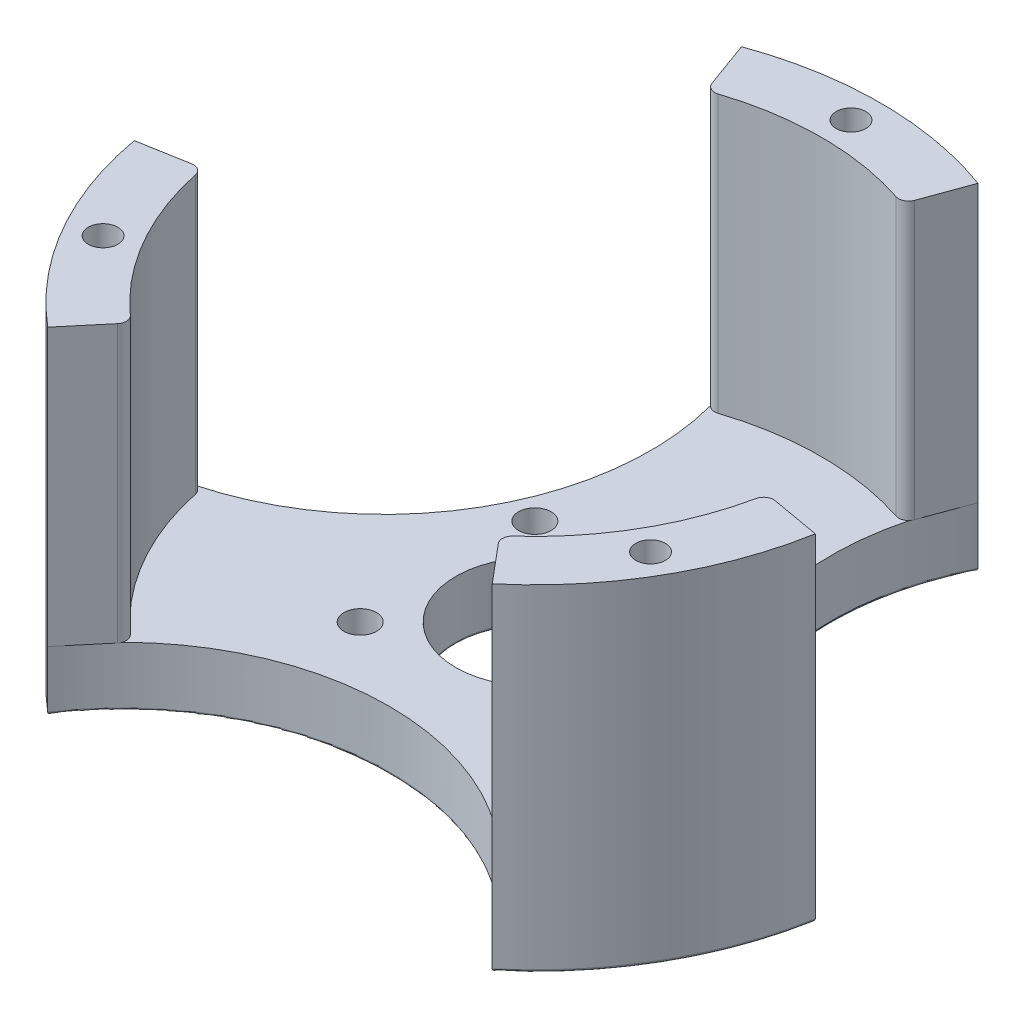
SolidWorks part; units mm, degrees
ref_plane "Front Plane" through (0, 0, 0) normal (0, 0, 1) x (1, 0, 0)
ref_plane "Top Plane" through (0, 0, 0) normal (0, 1, 0) x (1, 0, 0)
ref_plane "Right Plane" through (0, 0, 0) normal (1, 0, 0) x (0, 0, -1)
sketch "Sketch1" plane through (0, 0, 0) normal (0, 1, 0) x (1, 0, 0)
  line L1 (-8.8388, -8.8388) -> (8.8388, -8.8388) construction
  line L2 (-8.8388, -8.8388) -> (-8.8388, 8.8388) construction
  line L3 (-8.8388, 8.8388) -> (8.8388, 8.8388) construction
  line L4 (8.8388, -8.8388) -> (8.8388, 8.8388) construction
  line L5 (-8.8388, -8.8388) -> (8.8388, 8.8388) construction
  line L6 (-8.8388, 8.8388) -> (8.8388, -8.8388) construction
  circle A0 centre (0, 0) radius 35
  circle A1 centre (-8.8388, 8.8388) radius 1.65
  circle A2 centre (8.8388, 8.8388) radius 1.65
  circle A3 centre (8.8388, -8.8388) radius 1.65
  circle A4 centre (-8.8388, -8.8388) radius 1.65
  dimension "D1" = 70
  dimension "D4" = 3.3
  dimension "D2" = 12.5
extrude "Boss-Extrude1" add sketch "Sketch1" along normal blind 6
sketch "Sketch2" plane through (0, 6, 0) normal (0, 1, 0) x (1, 0, 0)
  line L0 (-11.9707, 32.8892) -> (0, 0) construction
  line L1 (0, 0) -> (11.9707, 32.8892) construction
  line L2 (0, -1000) -> (0, 49000) construction
  line L3 (-11.9707, 32.8892) -> (-9.9186, 27.2511)
  line L4 (9.9186, 27.2511) -> (11.9707, 32.8892)
  arc A0 (11.9707, 32.8892) -> (-11.9707, 32.8892) centre (0, 0) ccw
  circle A1 centre (0, 0) radius 35 construction
  arc A2 (9.9186, 27.2511) -> (-9.9186, 27.2511) centre (0, 0) ccw
  circle A3 centre (0, 32) radius 1.5
  dimension "D1" = 6
  dimension "D5" = 3
  dimension "D2" = 20
  dimension "D3" = 20
  dimension "D4" = 32
extrude "Boss-Extrude2" add sketch "Sketch2" along normal blind 28
sketch "Sketch16" plane through (0, 34, 0) normal (0, 1, 0) x (1, 0, 0)
  circle A0 centre (0, 32) radius 1.5
  circle A1 centre (0, 32) radius 1.5 construction
extrude "Cut-Extrude9" cut sketch "Sketch16" against normal through all
pattern_circular "CirPattern1" count 3 over 360 about axis through (0, 6, 0) along (0, -1, 0) of "Boss-Extrude2", "Cut-Extrude9" reverse direction yes
sketch "Sketch3" plane through (0, 6, 0) normal (0, 1, 0) x (1, 0, 0)
  circle A0 centre (0, 0) radius 8
  dimension "D1" = 16
extrude "Cut-Extrude1" cut sketch "Sketch3" against normal blind 10
sketch "Sketch4" plane through (0, 0, 0) normal (0, -1, 0) x (1, 0, 0)
  circle A0 centre (8.8388, 8.8388) radius 3.5
  circle A1 centre (8.8388, -8.8388) radius 3.5
  circle A2 centre (-8.8388, -8.8388) radius 3.5
  circle A3 centre (-8.8388, 8.8388) radius 3.5
  dimension "D1" = 7
extrude "Cut-Extrude2" cut sketch "Sketch4" against normal blind 3
sketch "Sketch5" plane through (0, 6, 0) normal (0, 1, 0) x (1, 0, 0)
  circle A1 centre (36.1765, 20.8865) radius 27.0183
extrude "Cut-Extrude3" cut sketch "Sketch5" against normal through all
pattern_circular "CirPattern2" count 3 over 360 about axis through (0, 6, 0) along (0, -1, 0) of "Cut-Extrude3" reverse direction yes
fillet "Fillet1" radius 0.25 16 edges at (0, 0, 14.7548) (30.3109, 0, 17.5) (9.204, 0, -22.4587) (21.5084, 0, 1.8034) (0, 0, -35) (-21.5084, 0, 1.8034) (-9.204, 0, -22.4587) (-30.3109, 0, 17.5) (0, 0, 8) (8.8388, 0, 5.3388) (5.6361, 0, -7.4274) (-5.6361, 0, -7.4274) (-8.8388, 0, 5.3388) (0, 0, -30.5) (26.4138, 0, 15.25) (-26.4138, 0, 15.25)
fillet "Fillet2" radius 1 6 edges at (28.5594, 20, 5.0358) (9.9186, 20, -27.2511) (-9.9186, 20, -27.2511) (18.6408, 20, 22.2153) (-28.5594, 20, 5.0358) (-18.6408, 20, 22.2153)
sketch "Sketch6" plane through (0, 34, 0) normal (0, 1, 0) x (1, 0, 0)
  line L0 (0, 32) -> (0, 0) construction
  line L1 (0, 0) -> (-27.7128, -16) construction
  line L2 (0, 0) -> (27.7128, -16) construction
  circle A0 centre (0, 0) radius 6
  circle A1 centre (15.5885, -9) radius 12
  circle A2 centre (0, 18) radius 12
  circle A3 centre (-15.5885, -9) radius 12
  point P7 (15.5885, -9)
  point P9 (0, 18)
  point P10 (-15.5885, -9)
  dimension "D1" = 12
  dimension "D2" = 24
sketch "Sketch7" plane through (0, 34, 0) normal (0, 1, 0) x (1, 0, 0)
  circle A0 centre (0, 0) radius 18
  circle A1 centre (0, 0) radius 13
  dimension "D1" = 26
  dimension "D2" = 5
ref_plane "Plane1" through (0, 29, 0) normal (0, 1, 0) x (1, 0, 0)
